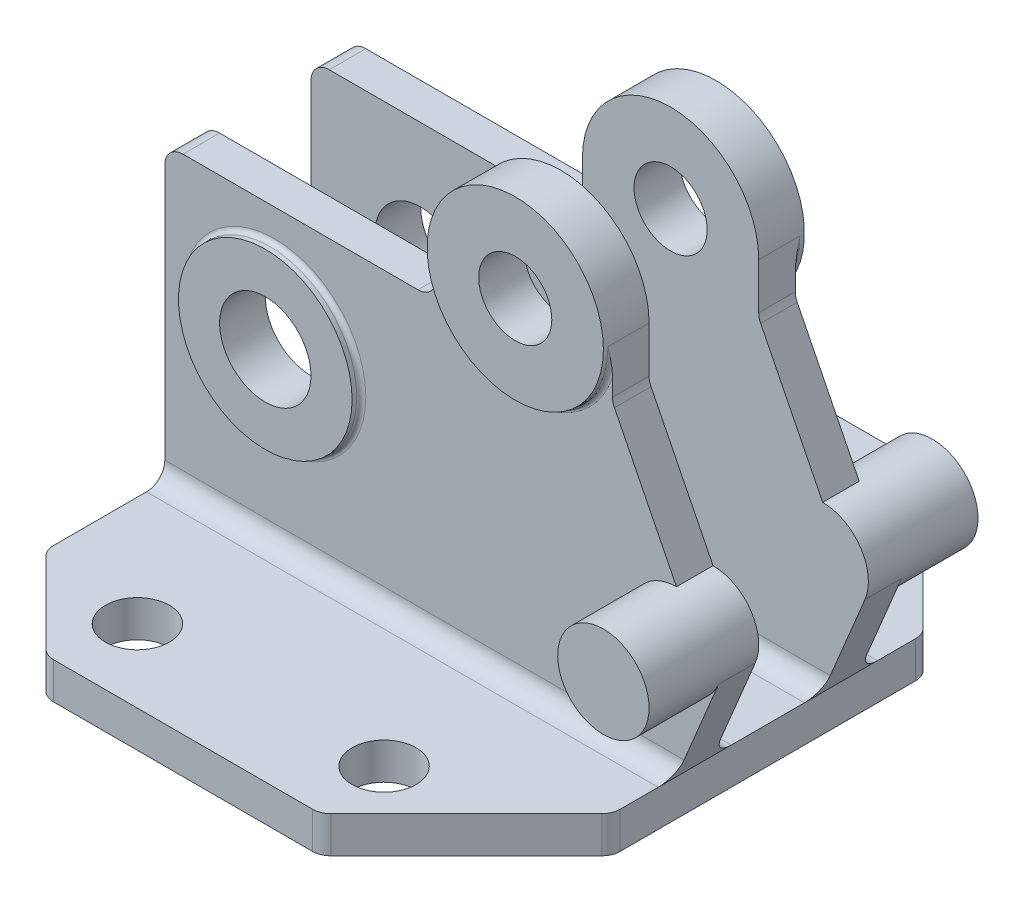
SolidWorks part; units mm, degrees
material "Cast Carbon Steel"
ref_plane "Front Plane" through (0, 0, 0) normal (0, 0, 1) x (1, 0, 0)
ref_plane "Top Plane" through (0, 0, 0) normal (0, 1, 0) x (1, 0, 0)
ref_plane "Right Plane" through (0, 0, 0) normal (1, 0, 0) x (0, 0, -1)
sketch "Sketch1" plane through (0, 0, 0) normal (0, 1, 0) x (1, 0, 0)
  line L0 (-27.4142, -23.5858) -> (-18.5858, -32.4142)
  line L1 (-17.1716, -33) -> (11.1716, -33)
  line L2 (-28, -22.1716) -> (-28, 23)
  line L3 (-18, 33) -> (12, 33)
  line L4 (28, -16.1716) -> (28, 16.1716)
  line L5 (-23.4098, -27.5902) -> (20.6557, 24.3443) construction
  line L6 (-23.4098, 27.5902) -> (20.6557, -24.3443) construction
  line L7 (12.5858, -32.4142) -> (27.4142, -17.5858)
  line L9 (-30.8, 0) -> (30.8, 0) construction
  line L10 (-18, -33) -> (12, -33)
  line L11 (-28, 22.1716) -> (-28, -23)
  line L12 (12.5858, 32.4142) -> (27.4142, 17.5858)
  line L13 (28, 17) -> (28, -17)
  line L14 (-27.4142, 23.5858) -> (-18.5858, 32.4142)
  line L15 (-17.1716, 33) -> (11.1716, 33)
  circle A0 centre (-16, -25) radius 3.5
  circle A1 centre (11, -25) radius 3.5
  circle A2 centre (11, 25) radius 3.5
  circle A3 centre (-16, 25) radius 3.5
  arc A4 (-17.1716, -33) -> (-18.5858, -32.4142) centre (-17.1716, -31) cw
  arc A5 (-28, -22.1716) -> (-27.4142, -23.5858) centre (-26, -22.1716) ccw
  arc A6 (12.5858, -32.4142) -> (11.1716, -33) centre (11.1716, -31) cw
  arc A7 (27.4142, -17.5858) -> (28, -16.1716) centre (26, -16.1716) ccw
  arc A8 (27.4142, 17.5858) -> (28, 16.1716) centre (26, 16.1716) cw
  arc A9 (12.5858, 32.4142) -> (11.1716, 33) centre (11.1716, 31) ccw
  arc A10 (-18.5858, 32.4142) -> (-17.1716, 33) centre (-17.1716, 31) cw
  arc A11 (-28, 22.1716) -> (-27.4142, 23.5858) centre (-26, 22.1716) cw
  point P0 (0, 0)
  point P2 (12, -33)
  point P4 (11, -25)
  point P5 (-16, -25)
  point P6 (-18, -33)
  point P8 (-28, -23)
  point P12 (28, -17)
  dimension "D1" = 2
extrude "Boss-Extrude2" add sketch "Sketch1" along normal blind 4 contours A11 L2 A5 L0 A4 L1 A6 L7 A7 L4 A8 L12 A9 L3 A10 L14 A2 A1 A0 A3 region at (-0.9261, 0, 0)
ref_plane "Plane1" through (0, 0, 6) normal (0, 0, 1) x (1, 0, 0)
sketch "Sketch4" plane through (0, 0, 6) normal (0, 0, 1) x (1, 0, 0)
  line L1 (-28, 4) -> (28, 4)
  line L2 (-28, 4) -> (-28, 34.0013)
  line L3 (-26, 36.0013) -> (-0.2929, 36.0013)
  line L4 (1.7071, 38.0013) -> (1.7071, 41.5014)
  line L5 (21, 41.5014) -> (21, 36.4722)
  line L6 (21.2112, 35.5777) -> (28, 22.0001)
  line L7 (28, 4) -> (32.6155, 15.0768)
  circle A0 centre (-16, 23) radius 5
  circle A1 centre (-16, 23) radius 9.5
  circle A2 centre (11.3536, 41.5014) radius 4
  circle A3 centre (11.3536, 41.5014) radius 9.6465
  arc A4 (-0.2929, 36.0013) -> (1.7071, 38.0013) centre (-0.2929, 38.0013) ccw
  arc A5 (-28, 34.0013) -> (-26, 36.0013) centre (-26, 34.0013) cw
  circle A6 centre (28, 17) radius 5.0001
  arc A7 (21, 36.4722) -> (21.2112, 35.5777) centre (23, 36.4722) ccw
  point P1 (28, 4)
  point P3 (0, 0)
  point P7 (-16, 23)
  point P12 (11.3536, 41.5014)
  point P16 (1.7071, 41.5014)
  point P25 (28, 17)
  point P28 (28, 22.0001)
  dimension "D1" = 2
  dimension "D2" = 2
  dimension "D3" = 2
  dimension "D4" = 10
  dimension "D5" = 19
  dimension "D6" = 8
  dimension "D7" = 19.2929
  dimension "D8" = 10.0002
ref_plane "Plane2" through (0, 0, -6) normal (0, 0, -1) x (-1, 0, 0)
sketch "Sketch6" plane through (0, 0, -6) normal (0, 0, -1) x (-1, 0, 0)
  line L0 (28, 4) -> (-28, 4)
  line L1 (-21.2112, 35.5777) -> (-28, 22)
  line L2 (28, 4) -> (28, 34.0013)
  line L3 (26, 36.0013) -> (0.2929, 36.0013)
  line L4 (-28, 4) -> (-32.6154, 15.0769)
  line L5 (-21, 36.4722) -> (-21, 41.5014)
  line L6 (-1.7071, 38.0013) -> (-1.7071, 41.5014)
  arc A0 (0.2929, 36.0013) -> (-1.7071, 38.0013) centre (0.2929, 38.0013) cw
  arc A1 (26, 36.0013) -> (28, 34.0013) centre (26, 34.0013) cw
  arc A2 (-21, 36.4722) -> (-21.2112, 35.5777) centre (-23, 36.4722) cw
  circle A3 centre (-28, 17) radius 5
  circle A4 centre (-11.3536, 41.5014) radius 9.6465
  circle A5 centre (-11.3536, 41.5014) radius 4
  circle A6 centre (16, 23) radius 5
  circle A7 centre (16, 23) radius 9.5
  point P39 (-28, 22.0001)
  point P40 (-32.6154, 15.0769)
  dimension "D2" = 8
  dimension "D3" = 10
  dimension "D4" = 19
  dimension "D5" = 32.6154
extrude "Boss-Extrude3" add sketch "Sketch6" along normal blind 5 separate body contours A4 A5 | A7 A6 region at (11.3536, 32.1277, -6) region at (-6.7687, 23, -6)
extrude "Boss-Extrude5" add sketch "Sketch6<10>" along normal blind 12 separate body contours A3 region at (28, 17, -6)
sketch "Sketch6<10>" plane through (0, 0, -6) normal (0, 0, -1) x (-1, 0, 0) same geometry as "Sketch6"
extrude "Boss-Extrude6" add sketch "Sketch6<11>" along normal blind 4 contours A4 L5 A2 L1 A3 L4 L0 L2 A1 L3 A0 L6 A7 region at (1.6349, 18.5687, -6)
sketch "Sketch6<11>" plane through (0, 0, -6) normal (0, 0, -1) x (-1, 0, 0) same geometry as "Sketch6"
fillet "Fillet2" radius 0.5 2 edges at (-25.5, 23, -10) (11.3536, 31.8549, -10)
extrude "Boss-Extrude7" add sketch "Sketch4" along normal blind 4 contours A7 L5 A3 L4 A4 L3 A5 L2 L1 L7 A6 L6 A1 region at (1.6349, 18.5687, 6)
extrude "Boss-Extrude8" add sketch "Sketch4<4>" along normal blind 5 contours A1 A0 | A3 A2 region at (11.3536, 50.875, 6) region at (-25.2313, 23, 6)
sketch "Sketch4<4>" plane through (0, 0, 6) normal (0, 0, 1) x (1, 0, 0) same geometry as "Sketch4"
extrude "Boss-Extrude9" add sketch "Sketch4<5>" along normal blind 12 contours A6 region at (28, 17, 6)
sketch "Sketch4<5>" plane through (0, 0, 6) normal (0, 0, 1) x (1, 0, 0) same geometry as "Sketch4"
fillet "Fillet3" radius 0.5 2 edges at (11.3536, 31.8549, 10) (-6.5, 23, 10)
fillet "Fillet4" radius 2 4 edges at (0, 4, -6) (0, 4, -10) (0, 4, 6) (0, 4, 10)
